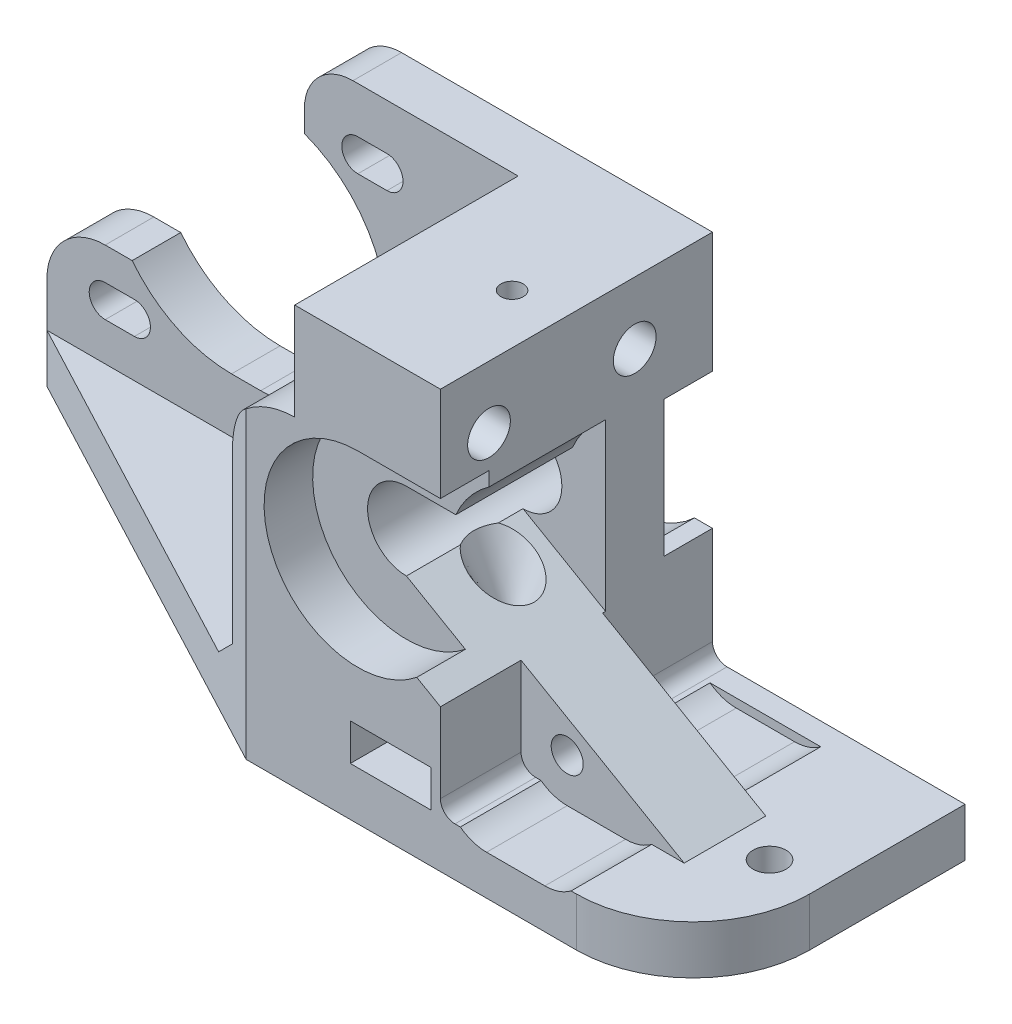
SolidWorks part; units mm, degrees
ref_plane "Front Plane" through (0, 0, 0) normal (0, 0, 1) x (1, 0, 0)
ref_plane "Top Plane" through (0, 0, 0) normal (0, 1, 0) x (1, 0, 0)
ref_plane "Right Plane" through (0, 0, 0) normal (1, 0, 0) x (0, 0, -1)
sketch "Sketch1" plane through (0, 0, 0) normal (0, 0, 1) x (1, 0, 0)
  line L0 (0, 0) -> (-60, 0) construction
  line L1 (-55, -23.6) -> (34.5, -23.6)
  line L2 (-55, -23.6) -> (-55, -8)
  line L3 (-28.5, 19.4) -> (34.5, 19.4)
  line L4 (34.5, -23.6) -> (34.5, 19.4)
  line L5 (-34.5, 0) -> (-34.5, -23.6) construction
  line L6 (-21.5, -17.6494) -> (-21.5, 14.65) construction
  line L7 (-20, 13) -> (-50, 13) construction
  line L8 (-23, 11.35) -> (-20, 11.35)
  line L9 (-23, 11.35) -> (-23, 14.65) construction
  line L10 (-23, 14.65) -> (-20, 14.65)
  line L11 (-20, 11.35) -> (-20, 14.65) construction
  line L12 (-36, -12.9851) -> (-33, -12.9851)
  line L14 (-20, -11.35) -> (-20, -14.65) construction
  line L15 (-23, -14.65) -> (-20, -14.65)
  line L16 (-23, -11.35) -> (-23, -14.65) construction
  line L17 (-23, -11.35) -> (-20, -11.35)
  line L18 (-46, -11.35) -> (-49, -11.35)
  line L19 (-46, -11.35) -> (-46, -14.65) construction
  line L20 (-46, -14.65) -> (-49, -14.65)
  line L21 (-49, -11.35) -> (-49, -14.65) construction
  line L26 (-28.5, 19.4) -> (-28.5, 12.1804)
  line L27 (-55, -8) -> (-46.228, -8)
  line L28 (-50, -13) -> (-19, -13) [skipped]
  line L29 (-47.5, 17.6494) -> (-47.5, -13.3506) [skipped]
  circle A0 centre (0, 0) radius 4
  circle A1 centre (-34.5, 0) radius 13 construction
  arc A2 (-46.228, -8) -> (-36, -12.9851) centre (-36, 0) ccw
  arc A3 (-20, 11.35) -> (-20, 14.65) centre (-20, 13) ccw
  arc A4 (-33, -12.9851) -> (-28.5, 12.1804) centre (-33, 0) ccw
  arc A5 (-23, 14.65) -> (-23, 11.35) centre (-23, 13) ccw
  arc A6 (-23, -11.35) -> (-23, -14.65) centre (-23, -13) ccw
  arc A7 (-20, -14.65) -> (-20, -11.35) centre (-20, -13) ccw
  arc A8 (-49, -11.35) -> (-49, -14.65) centre (-49, -13) ccw
  arc A9 (-46, -14.65) -> (-46, -11.35) centre (-46, -13) ccw
  dimension "D1" = 8
  dimension "D6" = 34.5
  dimension "D8" = 3.3
  dimension "D2" = 26
  dimension "D7" = 6
  dimension "D3" = 43
  dimension "D4" = 55
  dimension "D5" = 23.6
  dimension "D9" = 3
  dimension "D10" = 3
  dimension "D11" = 1.5
  dimension "D12" = 8
  dimension "D13" = 34.5
extrude "Boss-Extrude1" add sketch "Sketch1" along normal blind 28
sketch "Sketch2" plane through (0, 0, 28) normal (0, 0, 1) x (1, 0, 0)
  line L0 (-55, -8) -> (-55, -23.6) construction
  line L1 (-55, -18.6) -> (-14.5, -18.6)
  line L2 (-55, -18.6) -> (-55, 19.4)
  line L3 (-55, 19.4) -> (-14.5, 19.4)
  line L4 (-14.5, -18.6) -> (-14.5, 19.4)
  line L5 (34.5, 19.4) -> (-28.5, 19.4) construction
  line L6 (0, 0) -> (-55, 0) construction
  circle A0 centre (-34.5, 0) radius 17.3693 construction
  dimension "D1" = 20
  dimension "D2" = 18.6
  dimension "D3" = 34.5
extrude "Cut-Extrude1" cut sketch "Sketch2" against normal offset from surface (23 mm away) 5 up to face at (-21.5, -13, 0)
sketch "Sketch3" plane through (0, 0, 28) normal (0, 0, 1) x (1, 0, 0)
  circle A0 centre (0, 0) radius 9.65
  dimension "D1" = 19.3
extrude "Cut-Extrude2" cut sketch "Sketch3" against normal blind 5
ref_plane "Plane1" through (0, 0, 11) normal (0, 0, 1) x (1, 0, 0)
ref_plane "Plane2" through (0, -18.6, 0) normal (0, -1, 0) x (1, 0, 0)
ref_plane "Plane3" through (0, 0, 15.5) normal (0, 0, 1) x (1, 0, 0)
sketch "Sketch8" plane through (0, -23.6, 0) normal (0, -1, 0) x (1, 0, 0)
  circle A0 centre (3.375, 15.5) radius 1.15
  dimension "D1" = 2.3
  dimension "D2" = 3.375
  dimension "D3" = 15.5
extrude "Cut-Extrude7" cut sketch "Sketch8" against normal through all
sketch "Sketch9" plane through (34.5, 0, 0) normal (1, 0, 0) x (0, 0, -1)
  line L1 (-15.5, 23.65) -> (-15.5, -23.65) construction
  line L2 (0, 0) -> (-25.9492, 0) construction
  circle A0 centre (-8, 13) radius 2.2
  circle A1 centre (-23, 13) radius 2.2
  dimension "D1" = 4.4
  dimension "D2" = 7.5
  dimension "D3" = 13
  dimension "D4" = 7.5
extrude "Cut-Extrude8" cut sketch "Sketch9" against normal through all
sketch "Sketch10" plane through (-14.5, 0, 0) normal (-1, 0, 0) x (0, 0, 1)
  line L1 (5.1, 14.6743) -> (5.1, 11.3257)
  line L2 (5.1, 11.3257) -> (8, 9.6514)
  line L3 (8, 9.6514) -> (10.9, 11.3257)
  line L4 (10.9, 11.3257) -> (10.9, 14.6743)
  line L5 (10.9, 14.6743) -> (8, 16.3486)
  line L6 (8, 16.3486) -> (5.1, 14.6743)
  line L7 (25.9, 11.3257) -> (25.9, 14.6743)
  line L8 (25.9, 14.6743) -> (23, 16.3486)
  line L9 (23, 16.3486) -> (20.1, 14.6743)
  line L10 (20.1, 14.6743) -> (20.1, 11.3257)
  line L11 (20.1, 11.3257) -> (23, 9.6514)
  line L12 (23, 9.6514) -> (25.9, 11.3257)
  circle A0 centre (8, 13) radius 2.9 construction
  circle A1 centre (8, 13) radius 2.2 construction
  circle A2 centre (23, 13) radius 2.9 construction
  circle A5 centre (23, 13) radius 2.2 construction
  dimension "D1" = 5.8
extrude "Cut-Extrude9" cut sketch "Sketch10" against normal blind 11 and the other way blind 3
chamfer "Chamfer2" distance 3 angle 45 1 edges at (-14.5, -18.6, 16.5)
sketch "Sketch16" plane through (0, 0, 28) normal (0, 0, 1) x (1, 0, 0)
  line L0 (-17.5, -18.6) -> (-55, -18.6) construction
  line L1 (34.5, 19.4) -> (8.5, 19.4)
  line L2 (34.5, 19.4) -> (34.5, -18.6)
  line L3 (34.5, -18.6) -> (8.5, -18.6)
  line L4 (8.5, 19.4) -> (8.5, -18.6)
  dimension "D1" = 8.5
extrude "Cut-Extrude12" cut sketch "Sketch16" against normal through all
sketch "Sketch4" plane through (0, 0, 0) normal (0, 0, -1) x (-1, 0, 0)
  line L0 (0, 0) -> (-36.3115, 0) construction
  line L1 (-36.3115, -7) -> (-6.6425, -7)
  line L2 (-36.3115, -7) -> (-36.3115, 7)
  line L4 (-36.3115, 7) -> (-6.6425, 7)
  line L5 (-36.3115, -7) -> (0, 5) construction
  line L6 (-1.3153, -8.4204) -> (-36.3115, 7) construction
  arc A0 (-6.6425, -7) -> (-6.6425, 7) centre (0, 0) ccw
  dimension "D1" = 19.3
  dimension "D2" = 14
extrude "Cut-Extrude3" cut sketch "Sketch4" against normal blind 5
fillet "Fillet6" radius 1.5 1 edges at (8.5, -18.6, 14)
sketch "Sketch17" plane through (0, 0, 28) normal (0, 0, 1) x (1, 0, 0)
  line L0 (8.5, 19.4) -> (8.5, 4.5686) construction
  line L1 (0, 0) -> (19.7064, 0) construction
  line L2 (0, 4) -> (0, -4) construction
  line L3 (0, 4) -> (0, 9.65)
  line L4 (0, 9.65) -> (8.5, 9.65)
  line L6 (8.5, 9.65) -> (8.5, -8.9075)
  line L7 (8.5, -8.9075) -> (0, -4)
  arc A0 (8.5, 4.5686) -> (8.5, -4.5686) centre (0, 0) ccw construction
  arc A2 (0, -4) -> (0, 4) centre (0, 0) ccw
  circle A4 centre (0, 0) radius 4 construction
  dimension "D1" = 120
extrude "Cut-Extrude13" cut sketch "Sketch17" against normal up to surface (5 mm away) up to face at (-0.575, 0, 23)
ref_axis "Axis1" through (3.375, 19.4, 15.5) along (0, -1, 0)
sketch "Sketch20" plane through (0, 0, 15.5) normal (0, 0, 1) x (1, 0, 0)
  line L0 (3.375, -3.8) -> (3.375, -11.8) construction
  line L1 (3.375, 19.4) -> (3.375, 15.7335) construction
  line L2 (3.375, -11.8) -> (7.375, -3.8)
  line L3 (7.375, -3.8) -> (3.375, -3.8)
  line L4 (3.375, -3.8) -> (3.375, -11.8)
  dimension "D1" = 8
  dimension "D2" = 4
  dimension "D3" = 3.8
revolve "Cut-Revolve1" cut sketch "Sketch20" angle 360 mid plane about L0
sketch "Sketch21" plane through (0, 0, 15.5) normal (0, 0, 1) x (1, 0, 0)
  line L0 (14.7822, -11.8532) -> (7.25, -8.1858) construction
  line L1 (7.25, -8.1858) -> (7.25, -18.6)
  line L2 (7.25, -18.6) -> (25.2879, -18.6)
  line L3 (10, -18.6) -> (34.5, -18.6) construction
  line L4 (21.7997, -18.6) -> (15.7249, -12.5251) construction
  line L5 (6.0681, -7.5034) -> (8.5, -8.9075) construction
  line L6 (7.25, -8.1858) -> (25.2879, -18.6)
  line L7 (-15.4, -18.6) -> (15.4, -18.6) construction
  line L8 (8.5, -8.9075) -> (6.0681, -7.5034) construction
  circle A0 centre (13.25, -15) radius 1.65
  arc A1 (15.7249, -12.5251) -> (14.7822, -11.8532) centre (13.25, -15) ccw construction
  dimension "D2" = 3.3
  dimension "D5" = 3.5
  dimension "D1" = 13.25
  dimension "D3" = 15
  dimension "D4" = 6
  dimension "D6" = 45
extrude "Boss-Extrude3" add sketch "Sketch21" against normal blind 4.2 and the other way blind 4.2
sketch "Sketch15" plane through (0, -23.6, 0) normal (0, -1, 0) x (1, 0, 0)
  line L0 (-20.625, 15) -> (29.375, 15) construction
  circle A1 centre (-20.625, 15) radius 1.7
  circle A2 centre (29.375, 15) radius 1.7
  circle A3 centre (3.375, 15.5) radius 1.15 construction
  point P4 (3.375, 15.5)
  dimension "D2" = 3.4
  dimension "D1" = 50
extrude "Cut-Extrude11" cut sketch "Sketch15" against normal through all
sketch "Sketch22" plane through (0, 0, 19.7) normal (0, 0, 1) x (1, 0, 0)
  line L0 (13.25, -19.5) -> (19.25, -19.5)
  line L3 (19.25, -10.5) -> (13.25, -10.5)
  arc A0 (13.25, -10.5) -> (13.25, -19.5) centre (13.25, -15) ccw
  circle A1 centre (13.25, -15) radius 1.65 construction
  arc A2 (19.25, -19.5) -> (19.25, -10.5) centre (19.25, -15) ccw
  dimension "D1" = 9
  dimension "D2" = 6
extrude "Cut-Extrude14" cut sketch "Sketch22" along normal blind 9
mirror "Mirror1" about plane through (0, 0, 15.5) normal (0, 0, 1) of "Cut-Extrude14"
chamfer "Chamfer4" [suppressed] distance 8.5 distance2 10
fillet "Fillet1" radius 5 1 edges at (-28.5, 19.4, 2.5)
fillet "Fillet2" radius 6 1 edges at (-55, -8, 2.5)
fillet "Fillet4" radius 12 1 edges at (34.5, -21.1, 28)
sketch "Sketch23" plane through (0, -18.6, 0) normal (0, -1, 0) x (1, 0, 0)
  line L0 (-0.775, 28.722) -> (7.525, 28.722)
  line L3 (-0.775, 28.722) -> (-0.775, 13.104)
  line L4 (-0.775, 13.104) -> (3.375, 10.708)
  line L5 (3.375, 10.708) -> (7.525, 13.104)
  line L6 (7.525, 13.104) -> (7.525, 28.722)
  line L8 (3.375, 20.292) -> (-0.775, 17.896) [skipped]
  line L9 (7.525, 17.896) -> (3.375, 20.292) [skipped]
  circle A0 centre (3.375, 15.5) radius 4.25 construction
  dimension "D1" = 8.5
extrude "Cut-Extrude15" cut sketch "Sketch23" against normal blind 3.8
sketch "Sketch24" plane through (0, -23.6, 0) normal (0, -1, 0) x (1, 0, 0)
  line L0 (-10.475, 15.5) -> (17.225, 15.5) construction
  line L1 (23.65, 15.5) -> (-23.65, 15.5) construction
  circle A0 centre (3.375, 15.5) radius 12.5 construction
  circle A1 centre (-10.475, 15.5) radius 1.35
  circle A2 centre (17.225, 15.5) radius 1.35
  dimension "D1" = 25
  dimension "D2" = 2.7
extrude "Cut-Extrude16" [suppressed] cut sketch "Sketch24" against normal blind 10
sketch "Sketch25" [suppressed] plane through (0, -14.6, 0) normal (0, -1, 0) x (1, 0, 0)
  line L0 (-17.5, 18.4) -> (-17.5, 12.6)
  line L1 (20.125, 17.1743) -> (17.225, 18.8486)
  line L2 (17.225, 18.8486) -> (14.325, 17.1743)
  line L3 (14.325, 17.1743) -> (14.325, 13.8257)
  line L4 (14.325, 13.8257) -> (17.225, 12.1514)
  line L5 (17.225, 12.1514) -> (20.125, 13.8257)
  line L6 (20.125, 13.8257) -> (20.125, 17.1743)
  line L7 (-7.1264, 15.5) -> (-8.8007, 18.4)
  line L8 (-8.8007, 18.4) -> (-17.5, 18.4)
  line L9 (-17.5, 24.8276) -> (-17.5, 5) construction
  line L11 (-17.5, 12.6) -> (-8.8007, 12.6)
  line L12 (-8.8007, 12.6) -> (-7.1264, 15.5)
  line L14 (-13.8236, 15.5) -> (-12.1493, 12.6) [skipped]
  line L15 (-12.1493, 18.4) -> (-13.8236, 15.5) [skipped]
  circle A0 centre (17.225, 15.5) radius 2.9 construction
  circle A1 centre (-10.475, 15.5) radius 2.9 construction
  circle A2 centre (17.225, 15.5) radius 1.35 construction
  circle A3 centre (-10.475, 15.5) radius 1.35 construction
  dimension "D1" = 5.8
extrude "Cut-Extrude17" [suppressed] cut sketch "Sketch25" along normal blind 6 and the other way blind 3
sketch "Sketch26" plane through (0, -23.6, 0) normal (0, -1, 0) x (1, 0, 0)
  circle A0 centre (3.375, 15.5) radius 3.15
  circle A1 centre (3.375, 15.5) radius 1.15 construction
  dimension "D1" = 6.3
extrude "Cut-Extrude18" cut sketch "Sketch26" against normal up to next
sketch "Sketch27" plane through (0, 0, 23) normal (0, 0, 1) x (1, 0, 0)
  line L0 (8.5, -8.9075) -> (0, -4)
  line L1 (0, 4) -> (8.5, 4)
  line L2 (8.5, 9.65) -> (8.5, -8.9075) construction
  line L3 (8.5, 4) -> (8.5, -8.9075)
  line L4 (8.5, -8.9075) -> (8.5609, -8.8509)
  line L5 (6.0681, -7.5034) -> (8.5, -8.9075) construction
  arc A0 (0, 4) -> (0, -4) centre (0, 0) ccw
extrude "Cut-Extrude19" cut sketch "Sketch27" against normal blind 12 contours L0 A0 L1 L3
sketch "Sketch28" plane through (0, 0, 15.5) normal (0, 0, 1) x (1, 0, 0)
  line L0 (0, 0) -> (14.25, 0) construction
  line L1 (3.375, 19.4) -> (3.375, 15.7335) construction
  circle A0 centre (14.25, 0) radius 10
  dimension "D1" = 20
  dimension "D2" = 10.875
extrude "Cut-Extrude20" cut sketch "Sketch28" against normal up to surface (4.5 mm away) and the other way through all up to face at (5.25, -1.2269, 11)
sketch "Sketch29" plane through (-14.5, 0, 0) normal (-1, 0, 0) x (0, 0, 1)
  line L0 (5, -12.9851) -> (5, 12.1804) construction
  line L1 (28, 19.4) -> (5, 19.4)
  line L2 (28, 19.4) -> (28, 9.4)
  line L3 (28, 9.4) -> (5, 9.4)
  line L4 (5, 19.4) -> (5, 9.4)
  dimension "D1" = 10
extrude "Cut-Extrude21" cut sketch "Sketch29" against normal blind 8
fillet "Fillet7" radius 8 1 edges at (-14.5, 9.4, 16.5)
chamfer "Chamfer1" distance 23 distance2 43.5 1 edges at (-55, -21.1, 28) first distance on face at (-55, -18.7333, 11)
